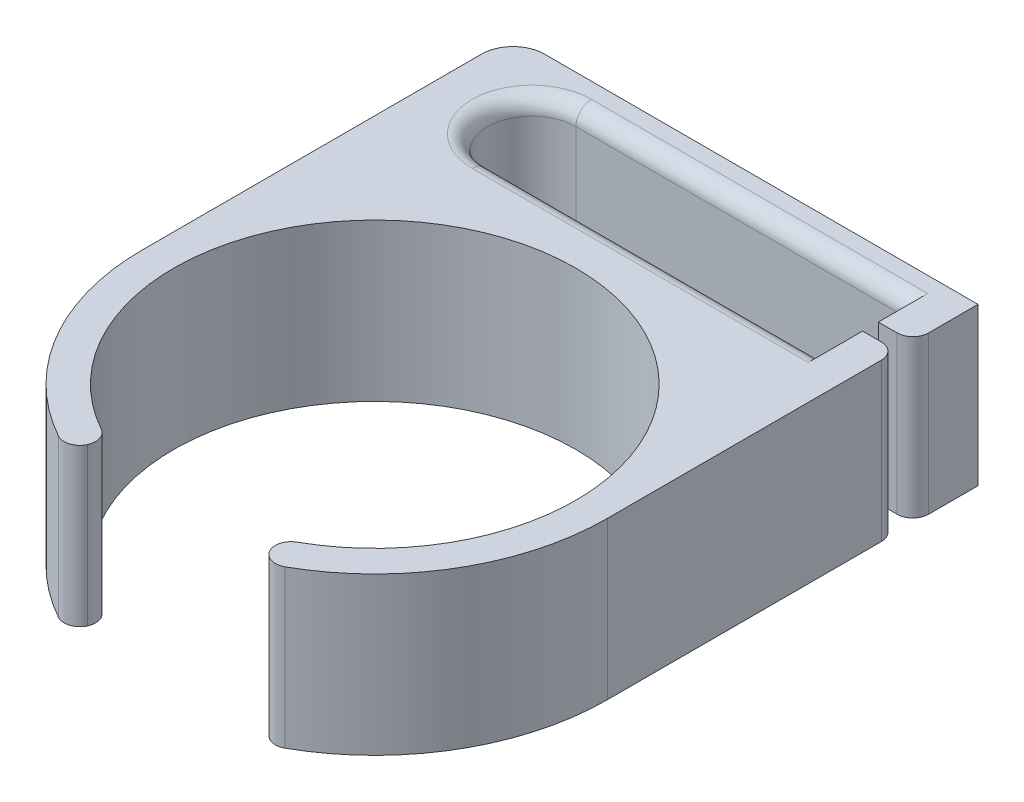
SolidWorks part; units mm, degrees
ref_plane "Front Plane" through (0, 0, 0) normal (0, 0, 1) x (1, 0, 0)
ref_plane "Top Plane" through (0, 0, 0) normal (0, 1, 0) x (1, 0, 0)
ref_plane "Right Plane" through (0, 0, 0) normal (1, 0, 0) x (0, 0, -1)
sketch "Sketch2" plane through (0, 0, 0) normal (0, 1, 0) x (1, 0, 0)
  line L0 (0, 14.8) -> (14.8, 14.8)
  line L1 (14.8, 14.8) -> (0, 14.8)
  line L2 (-14.8, 0) -> (-14.8, 14.8)
  line L3 (-14.8, 14.8) -> (0, 14.8)
  line L4 (-14.8, 14.8) -> (-14.8, 23.6)
  line L5 (-14.8, 23.6) -> (14.8, 23.6)
  line L6 (14.8, 14.8) -> (14.8, 18.4532)
  line L7 (14.8, 18.4532) -> (12.6, 18.4532)
  line L8 (12.6, 18.4532) -> (12.6, 16)
  line L9 (12.6, 16) -> (-14.8, 16)
  line L10 (14.8, 19.4532) -> (12.6, 19.4532)
  line L11 (14.8, 23.6) -> (14.8, 19.4532)
  line L12 (14.8, 14.8) -> (14.8, 0)
  line L13 (12.6, 19.4532) -> (12.6, 21.6)
  line L14 (12.6, 21.6) -> (-14.8, 21.6)
  line L15 (-8.8, 14.8) -> (-8.8, 23.6) construction
  line L16 (0, 0) -> (0, -21.9095)
  line L17 (0, 0) -> (-10.2165, -21.9095)
  line L18 (0, 0) -> (10.2165, -21.9095)
  line L19 (-10.2165, -21.9095) -> (10.2165, -21.9095)
  line L20 (13.7, 18.4532) -> (13.7, 19.4532) construction
  arc A0 (5.4095, -11.6007) -> (-5.4095, -11.6007) centre (0, 0) ccw
  arc A1 (6.2548, -13.4134) -> (-6.2548, -13.4134) centre (0, 0) ccw
  arc A2 (-8.8, 21.6) -> (-8.8, 16) centre (-8.8, 18.8) ccw
  point P32 (13.7, 18.9532)
  dimension "D1" = 25.6
  dimension "D2" = 29.6
  dimension "D3" = 2
  dimension "D7" = 21.9095
  dimension "D4" = 5.6
  dimension "D5" = 2.2
  dimension "D6" = 2.2
  dimension "D8" = 25
  dimension "D9" = 25
  dimension "D10" = 4
  dimension "D11" = 6
  dimension "D12" = 1
  dimension "D13" = 4.1532
extrude "Boss-Extrude1" add sketch "Sketch2" along normal blind 10 contours A1 A0 | A1 L12 L0 | L15 L3 L0 L6 L7 L8 L9 | L15 L14 L13 L10 L11 L5 | A1 L3 L2 | L3 L15 L9 L4 | A2 L14 L4 L9 | L14 L15 L5 L4 region at (4.7127, 0, -15.6924) region at (-11.4942, 0, -11.4942) region at (11.4942, 0, -11.4942) region at (10.176, 0, -10.176) region at (-11.8, 0, -15.4) region at (-12.8482, 0, -18.8) region at (3.9733, 0, -22.4114) region at (-11.8, 0, -22.6)
fillet "Fillet1" radius 2 1 edges at (-14.8, 5, -23.6)
fillet "Fillet2" radius 1 12 edges at (1.9, 0, -21.6) (-11.6, 0, -18.8) (1.9, 10, -21.6) (-11.6, 10, -18.8) (1.9, 0, -16) (1.9, 10, -16) (14.8, 5, -19.4532) (14.8, 5, -18.4532) (5.4095, 5, 11.6007) (6.2548, 5, 13.4134) (-6.2548, 5, 13.4134) (-5.4095, 5, 11.6007)
